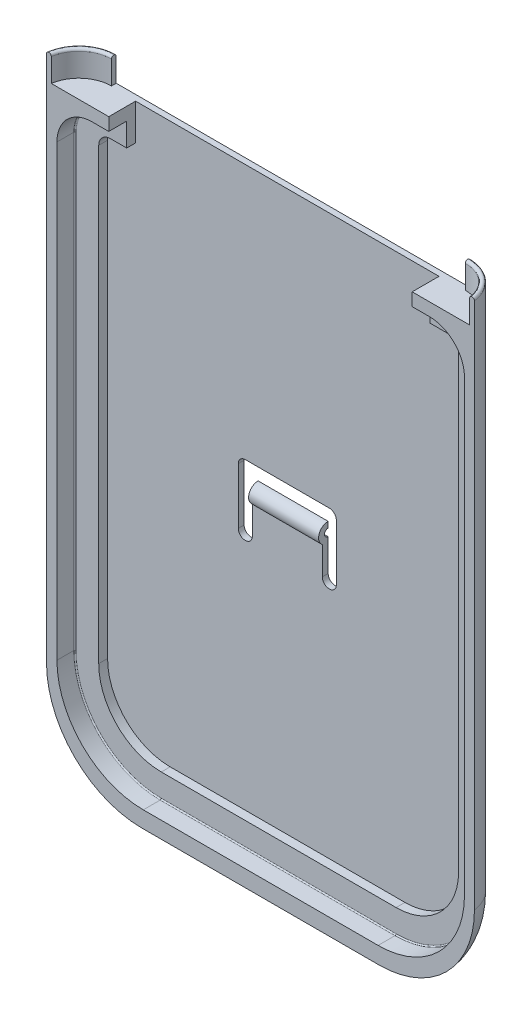
SolidWorks part; units mm, degrees
ref_plane "Front" through (0, 0, 0) normal (0, 0, 1) x (1, 0, 0)
ref_plane "Top" through (0, 0, 0) normal (0, 1, 0) x (1, 0, 0)
ref_plane "Right" through (0, 0, 0) normal (1, 0, 0) x (0, 0, -1)
ref_plane "Plane4" through (0, 0, -6.7818) normal (0, 0, 1) x (1, 0, 0)
sketch "Sketch14" plane through (0, 0, -6.7818) normal (0, 0, 1) x (1, 0, 0)
  line L3 (23.2853, 10.3821) -> (23.2853, 68.0401)
  line L4 (-12.9032, 0) -> (12.9032, 0)
  line L5 (-23.2853, 68.0401) -> (-23.2853, 10.3821)
  line L6 (23.2853, 68.0401) -> (-23.2853, 68.0401)
  arc A2 (12.9032, 0) -> (23.2853, 10.3821) centre (12.9032, 10.3821) ccw
  arc A3 (-23.2853, 10.3821) -> (-12.9032, 0) centre (-12.9032, 10.3821) ccw
  dimension "D3" = 10.3821
  dimension "D4" = 10.3821
  dimension "D1" = 46.5706
  dimension "D2" = 68.0401
extrude "Boss-Extrude11" add sketch "Sketch14" along normal blind 3.556 separate body
fillet "Fillet37" radius 4.064 5 edges at (-23.2853, 39.2111, -6.7818) (-20.2445, 3.0409, -6.7818) (0, 0, -6.7818) (20.2445, 3.0409, -6.7818) (23.2853, 39.2111, -6.7818)
sketch "Sketch15" plane through (0, 0, -3.2258) normal (0, 0, 1) x (1, 0, 0)
  line L0 (0, -50) -> (0, 50) construction
  line L3 (-22.1488, 63.8491) -> (22.1995, 63.8491)
  line L4 (22.1995, 63.8491) -> (22.1995, 11.1949)
  line L5 (12.8015, 1.7969) -> (-12.7508, 1.7969)
  line L6 (23.2853, 68.0401) -> (-23.2853, 68.0401) construction
  line L8 (-12.9032, 0) -> (12.9032, 0) construction
  line L11 (-22.1488, 63.8491) -> (-22.1488, 11.1949)
  arc A1 (12.8015, 1.7969) -> (22.1995, 11.1949) centre (12.8015, 11.1949) ccw
  arc A2 (-12.7508, 1.7969) -> (-22.1488, 11.1949) centre (-12.7508, 11.1949) cw
  point P19 (0, 63.8491)
  dimension "D3" = 9.398
  dimension "D1" = 4.191
  dimension "D2" = 22.1995
  dimension "D4" = 1.7969
  dimension "D5" = 22.1488
extrude "Cut-Extrude2" cut sketch "Sketch15" against normal blind 1.9558
sketch "Sketch16" plane through (0, 0, -5.1816) normal (0, 0, 1) x (1, 0, 0)
  line L4 (19.6088, 61.3091) -> (19.6088, 11.1949)
  line L5 (12.8016, 4.3877) -> (-12.7508, 4.3877)
  line L6 (-19.558, 11.1949) -> (-19.558, 61.3091)
  line L7 (-19.558, 61.3091) -> (19.6088, 61.3091)
  line L10 (22.1995, 63.8491) -> (-22.1488, 63.8491) construction
  line L11 (-12.7508, 1.7969) -> (12.8015, 1.7969) construction
  arc A0 (12.8016, 4.3877) -> (19.6088, 11.1949) centre (12.8016, 11.1949) ccw
  arc A1 (-12.7508, 4.3877) -> (-19.558, 11.1949) centre (-12.7508, 11.1949) cw
  dimension "D2" = 6.8072
  dimension "D1" = 19.6088
  dimension "D3" = 2.54
  dimension "D4" = 2.5908
  dimension "D5" = 19.558
extrude "Cut-Extrude3" cut sketch "Sketch16" against normal blind 0.9652
ref_plane "Plane1" through (13.8684, 0, 0) normal (1, 0, 0) x (0, 0, -1)
ref_plane "Plane6" through (0, 0, -1.8288) normal (0, 0, -1) x (-1, 0, 0)
sketch "Sketch18" plane through (0, 0, -1.8288) normal (0, 0, 1) x (1, 0, 0)
  line L4 (-19.558, 21.5886) -> (19.6088, 21.5886)
  line L5 (19.6088, 21.9696) -> (-19.558, 21.9696)
  line L6 (17.5599, 3.1939) -> (-19.1347, 3.1939)
  line L7 (-20.3708, 7.1055) -> (-20.3708, 61.7257)
  line L8 (-20.3708, 61.7257) -> (20.4216, 61.7257)
  line L9 (-19.558, 39.1705) -> (19.6088, 39.1705)
  line L10 (19.6088, 39.5515) -> (-19.558, 39.5515)
  line L11 (20.4216, 8.7411) -> (20.4216, 61.7257)
  line L12 (19.6088, 39.5515) -> (19.6088, 61.3091)
  line L13 (19.6088, 21.9696) -> (19.6088, 39.1705)
  line L14 (-19.558, 21.5886) -> (-19.558, 11.1949)
  line L15 (-19.558, 39.1705) -> (-19.558, 21.9696)
  line L16 (-12.7508, 4.3877) -> (12.8016, 4.3877)
  line L17 (19.6088, 11.1949) -> (19.6088, 61.3091)
  line L18 (19.6088, 61.3091) -> (-19.558, 61.3091)
  line L19 (-19.558, 61.3091) -> (-19.558, 11.1949)
  line L20 (-12.7508, 4.3877) -> (12.8016, 4.3877)
  line L21 (19.6088, 11.1949) -> (19.6088, 21.5886)
  line L22 (19.6088, 61.3091) -> (-19.558, 61.3091)
  line L23 (-19.558, 61.3091) -> (-19.558, 39.5515)
  arc A2 (-20.3708, 7.1055) -> (-19.1347, 3.1939) centre (-13.5636, 7.1055) ccw
  arc A3 (17.5599, 3.1939) -> (20.4216, 8.7411) centre (13.6144, 8.7411) ccw
  arc A4 (-19.558, 11.1949) -> (-12.7508, 4.3877) centre (-12.7508, 11.1949) ccw
  arc A5 (-19.558, 11.1949) -> (-12.7508, 4.3877) centre (-12.7508, 11.1949) ccw
  arc A6 (12.8016, 4.3877) -> (19.6088, 11.1949) centre (12.8016, 11.1949) ccw
  arc A7 (12.8016, 4.3877) -> (19.6088, 11.1949) centre (12.8016, 11.1949) ccw
  dimension "D4" = 6.8072
  dimension "D6" = 6.8072
  dimension "D2" = 0.4166
  dimension "D3" = 0.8128
  dimension "D5" = 1.1938
  dimension "D7" = 0.8128
  dimension "D8" = 36.6946
  dimension "D9" = 0.4233
  dimension "D10" = 17.2009
  dimension "D11" = 0.381
  dimension "D12" = 0.381
  dimension "D13" = 17.5819
  dimension "D1" = 0
extrude "Boss-Extrude12" [suppressed] add sketch "Sketch18" against normal up to surface (4.445 mm away) up to face at (0.0254, 25.1607, -6.1468)
ref_plane "Plane5" [suppressed] through (-0.0255, 0, 0) normal (-1, 0, 0) x (0, 0, 1)
sketch "Sketch19" [suppressed] plane through (0, 0, 0) normal (1, 0, 0) x (0, 0, -1)
  line L2 (4.2171, 0.7825) -> (1.8288, 0.7825)
  line L3 (6.1468, 2.7685) -> (6.1468, 7.2833)
  line L5 (1.8288, 7.2833) -> (5.1816, 7.2833) construction
  line L6 (1.8288, 7.2833) -> (6.1468, 7.2833)
  line L7 (1.8288, 7.2833) -> (1.8288, 0.7825)
  arc A0 (4.2171, 0.7825) -> (5.2167, 1.1561) centre (4.2171, 2.3065) ccw construction
  arc A1 (5.2167, 1.1561) -> (5.8928, 1.9261) centre (2.7178, 4.0321) ccw construction
  arc A2 (5.8928, 1.9261) -> (6.1468, 2.7685) centre (4.6228, 2.7685) ccw construction
  arc A3 (4.2171, 0.7825) -> (5.2167, 1.1561) centre (4.2171, 2.3065) ccw
  arc A4 (5.2167, 1.1561) -> (5.8928, 1.9261) centre (2.7178, 4.0321) ccw
  arc A5 (5.8928, 1.9261) -> (6.1468, 2.7685) centre (4.6228, 2.7685) ccw
extrude "Cut-Extrude9" [suppressed] cut sketch "Sketch19" against normal blind 12.8016 and the other way blind 6.35
sketch "Sketch1" [suppressed] plane through (13.8684, 0, 0) normal (1, 0, 0) x (0, 0, -1)
  line L0 (3.3744, 8.4771) -> (6.2738, 8.4771)
  line L1 (6.2738, 8.4771) -> (6.2738, 11.292)
  line L2 (6.2738, 8.4771) -> (1.8288, 8.4771) construction
  line L3 (6.2738, 25.678) -> (6.2738, 9.2391) construction
  line L4 (6.2738, 25.678) -> (1.8288, 25.678) construction
  line L5 (3.3731, 25.678) -> (6.2738, 25.678)
  line L6 (6.2738, 25.678) -> (6.2738, 22.7773)
  line L7 (6.2738, 26.059) -> (1.8288, 26.059) construction
  line L8 (6.2738, 43.2599) -> (6.2738, 26.059) construction
  line L9 (3.3731, 26.059) -> (6.2738, 26.059)
  line L10 (6.2738, 26.059) -> (6.2738, 28.9597)
  line L11 (6.2738, 43.2599) -> (1.8288, 43.2599) construction
  line L12 (3.3731, 43.2599) -> (6.2738, 43.2599)
  line L13 (6.2738, 43.2599) -> (6.2738, 40.3592)
  line L15 (6.2738, 43.6409) -> (1.8288, 43.6409) construction
  line L16 (6.2738, 43.6409) -> (6.2738, 60.8418) construction
  line L17 (3.3731, 43.6409) -> (6.2738, 43.6409)
  line L18 (6.2738, 43.6409) -> (6.2738, 46.5416)
  line L19 (6.2738, 60.8418) -> (3.3731, 60.8418)
  line L20 (6.2738, 60.8418) -> (1.8288, 60.8418) construction
  line L21 (6.2738, 60.8418) -> (6.2738, 57.9411)
  arc A0 (6.2738, 11.292) -> (3.3744, 8.4771) centre (3.3744, 11.3778) cw
  arc A1 (3.3731, 25.678) -> (6.2738, 22.7773) centre (3.3731, 22.7773) cw
  arc A2 (3.3731, 26.059) -> (6.2738, 28.9597) centre (3.3731, 28.9597) ccw
  arc A3 (3.3731, 43.2599) -> (6.2738, 40.3592) centre (3.3731, 40.3592) cw
  arc A4 (3.3731, 43.6409) -> (6.2738, 46.5416) centre (3.3731, 46.5416) ccw
  arc A5 (3.3731, 60.8418) -> (6.2738, 57.9411) centre (3.3731, 57.9411) cw
  dimension "D1" = 2.9007
  dimension "D2" = 2.8994
extrude "Boss-Extrude1" [suppressed] add sketch "Sketch1" against normal blind 0.762
sketch "Sketch22" plane through (0, 68.0401, 0) normal (0, 1, 0) x (1, 0, 0)
  line L3 (-19.2532, 6.7818) -> (-19.2532, 6.2611)
  line L4 (19.2532, 6.2611) -> (19.2532, 6.7818)
  line L5 (22.1995, 3.2258) -> (-22.1488, 3.2258) construction
  line L7 (22.7599, 3.2258) -> (-22.7599, 3.2258)
  line L8 (19.2532, 6.7818) -> (-19.2532, 6.7818)
  line L10 (19.2532, 6.7818) -> (-19.2532, 6.7818) construction
  line L11 (0, 0) -> (0, 6.7818) construction
  arc A7 (22.7687, 3.1607) -> (19.2532, 6.2611) centre (19.2532, 2.7178) ccw
  arc A8 (22.7599, 3.2258) -> (19.2532, 6.2611) centre (19.2532, 2.7178) ccw
  arc A9 (-19.2532, 6.2611) -> (-22.7687, 3.1607) centre (-19.2532, 2.7178) ccw
  arc A10 (-19.2532, 6.2611) -> (-22.7599, 3.2258) centre (-19.2532, 2.7178) ccw
  dimension "D2" = 0.5207
  dimension "D5" = 0.5207
  dimension "D1" = 38.5064
extrude "Cut-Extrude7" cut sketch "Sketch22" against normal blind 2.794
fillet "Fillet38" [suppressed] type full round
fillet "Fillet39" [suppressed] type full round
ref_plane "Plane2" [suppressed] through (29.6672, 0, 0) normal (-1, 0, 0) x (0, -1, 0)
ref_plane "Plane10" [suppressed] through (6.35, 0, 0) normal (1, 0, 0) x (0, 0, -1)
sketch "Sketch2" [suppressed] plane through (6.35, 0, 0) normal (-1, 0, 0) x (0, -1, 0)
  line L0 (-11.292, -6.2738) -> (-8.4771, -6.2738) construction
  line L1 (-8.4771, -6.2738) -> (-8.4771, -3.3744) construction
  line L5 (-25.678, -3.3731) -> (-25.678, -6.2738) construction
  line L6 (-25.678, -6.2738) -> (-22.7773, -6.2738) construction
  line L9 (-28.9597, -6.2738) -> (-26.059, -6.2738) construction
  line L10 (-26.059, -6.2738) -> (-26.059, -3.3731) construction
  line L12 (-43.2599, -3.3731) -> (-43.2599, -6.2738) construction
  line L13 (-43.2599, -6.2738) -> (-40.3592, -6.2738) construction
  line L18 (-46.5416, -6.2738) -> (-43.6409, -6.2738) construction
  line L19 (-43.6409, -6.2738) -> (-43.6409, -3.3731) construction
  line L20 (-60.8418, -6.2738) -> (-57.9411, -6.2738) construction
  line L21 (-60.8418, -3.3731) -> (-60.8418, -6.2738) construction
  line L22 (-11.292, -6.2738) -> (-8.4771, -6.2738)
  line L23 (-8.4771, -6.2738) -> (-8.4771, -3.3744)
  line L24 (-25.678, -3.3731) -> (-25.678, -6.2738)
  line L25 (-25.678, -6.2738) -> (-22.7773, -6.2738)
  line L26 (-28.9597, -6.2738) -> (-26.059, -6.2738)
  line L27 (-26.059, -6.2738) -> (-26.059, -3.3731)
  line L28 (-43.2599, -3.3731) -> (-43.2599, -6.2738)
  line L29 (-43.2599, -6.2738) -> (-40.3592, -6.2738)
  line L30 (-46.5416, -6.2738) -> (-43.6409, -6.2738)
  line L31 (-43.6409, -6.2738) -> (-43.6409, -3.3731)
  line L32 (-60.8418, -6.2738) -> (-57.9411, -6.2738)
  line L33 (-60.8418, -3.3731) -> (-60.8418, -6.2738)
  arc A0 (-11.292, -6.2738) -> (-8.4771, -3.3744) centre (-11.3778, -3.3744) ccw construction
  arc A1 (-25.678, -3.3731) -> (-22.7773, -6.2738) centre (-22.7773, -3.3731) ccw construction
  arc A2 (-28.9597, -6.2738) -> (-26.059, -3.3731) centre (-28.9597, -3.3731) ccw construction
  arc A3 (-43.2599, -3.3731) -> (-40.3592, -6.2738) centre (-40.3592, -3.3731) ccw construction
  arc A6 (-46.5416, -6.2738) -> (-43.6409, -3.3731) centre (-46.5416, -3.3731) ccw construction
  arc A7 (-60.8418, -3.3731) -> (-57.9411, -6.2738) centre (-57.9411, -3.3731) ccw construction
  arc A8 (-11.292, -6.2738) -> (-8.4771, -3.3744) centre (-11.3778, -3.3744) ccw
  arc A9 (-25.678, -3.3731) -> (-22.7773, -6.2738) centre (-22.7773, -3.3731) ccw
  arc A10 (-28.9597, -6.2738) -> (-26.059, -3.3731) centre (-28.9597, -3.3731) ccw
  arc A11 (-43.2599, -3.3731) -> (-40.3592, -6.2738) centre (-40.3592, -3.3731) ccw
  arc A12 (-46.5416, -6.2738) -> (-43.6409, -3.3731) centre (-46.5416, -3.3731) ccw
  arc A13 (-60.8418, -3.3731) -> (-57.9411, -6.2738) centre (-57.9411, -3.3731) ccw
extrude "Boss-Extrude2" [suppressed] add sketch "Sketch2" against normal blind 0.762
sketch "Sketch3" [suppressed] plane through (6.35, 0, 0) normal (-1, 0, 0) x (0, -1, 0)
  line L0 (-60.8418, -3.3744) -> (-60.8418, -6.2738)
  line L1 (-60.8418, -6.2738) -> (-58.0269, -6.2738)
  line L2 (-60.8418, -6.2738) -> (-60.8418, -1.8288) construction
  line L3 (-60.8418, -6.2738) -> (-43.6409, -6.2738) construction
  line L4 (-43.6409, -6.2738) -> (-43.6409, -1.8288) construction
  line L5 (-43.6409, -3.3731) -> (-43.6409, -6.2738)
  line L6 (-43.6409, -6.2738) -> (-46.5416, -6.2738)
  arc A0 (-58.0269, -6.2738) -> (-60.8418, -3.3744) centre (-57.9411, -3.3744) cw
  arc A1 (-43.6409, -3.3731) -> (-46.5416, -6.2738) centre (-46.5416, -3.3731) cw
  dimension "D1" = 2.9007
  dimension "D2" = 2.8149
sketch "Sketch9" [suppressed] plane through (0, 0, -6.2738) normal (0, 0, 1) x (1, 0, 0)
  line L0 (16.4084, 37.1994) -> (17.0434, 37.1994)
  line L1 (17.0434, 37.1994) -> (17.0434, 32.1194)
  line L2 (17.0434, 32.1194) -> (16.4084, 32.1194)
  line L3 (16.4084, 32.1194) -> (16.4084, 37.1994)
  line L4 (-18.796, 34.6594) -> (16.4084, 34.6594) construction
  line L5 (50, 0) -> (-50, 0) construction
  line L7 (18.7452, 26.059) -> (18.7452, 43.2599) construction
  line L9 (16.4084, 19.6176) -> (17.0434, 19.6176)
  line L10 (16.4084, 19.6176) -> (16.4084, 14.5376)
  line L11 (16.4084, 14.5376) -> (17.0434, 14.5376)
  line L12 (17.0434, 19.6176) -> (17.0434, 14.5376)
  line L13 (16.4084, 54.7813) -> (17.0434, 54.7813)
  line L14 (16.4084, 54.7813) -> (16.4084, 49.7013)
  line L15 (16.4084, 49.7013) -> (17.0434, 49.7013)
  line L16 (17.0434, 54.7813) -> (17.0434, 49.7013)
  line L18 (-18.796, 43.2599) -> (-18.796, 26.059) construction
  line L20 (-18.796, 52.2413) -> (16.4084, 52.2413) construction
  line L22 (-18.796, 17.0776) -> (16.4084, 17.0776) construction
  dimension "D1" = 1.7018
  dimension "D2" = 0.635
  dimension "D3" = 52.2413
  dimension "D4" = 5.08
  dimension "D5" = 17.0776
  dimension "D6" = 5.08
  dimension "D8" = 5.08
extrude "Boss-Extrude8" [suppressed] add sketch "Sketch9" along normal blind 3.175
sketch "Sketch8" plane through (0, 0, -3.2258) normal (0, 0, 1) x (1, 0, 0)
  line L0 (-16.51, 65.2461) -> (-16.51, 64.6111)
  line L1 (-16.51, 64.6111) -> (16.51, 64.6111)
  line L2 (16.51, 64.6111) -> (16.51, 65.2461)
  line L3 (16.51, 65.2461) -> (-16.51, 65.2461)
  line L4 (0, -50) -> (0, 50) construction
  line L6 (-22.7599, 65.2461) -> (22.7599, 65.2461) construction
  point P8 (0, 64.6111)
  dimension "D1" = 0.635
  dimension "D3" = 33.02
extrude "Cut-Extrude1" [suppressed] cut sketch "Sketch8" against normal blind 1.9558
mirror "Mirror1" [suppressed] about plane through (0, 0, 0) normal (1, 0, 0)
sketch "Sketch25" [suppressed] plane through (0, 0, 0) normal (1, 0, 0) x (0, 0, -1)
  line L0 (3.3731, 25.678) -> (3.3731, 26.059)
  line L1 (-0.2883, 28.0707) -> (0.612, 28.0707)
  line L2 (0.612, 23.6663) -> (-0.2883, 23.6663)
  line L3 (6.2738, 26.059) -> (1.8288, 26.059) construction
  line L6 (-0.2883, 41.2482) -> (-0.2883, 45.6526)
  line L7 (0.612, 45.6526) -> (-0.2883, 45.6526)
  line L8 (-0.2883, 41.2482) -> (0.612, 41.2482)
  line L9 (3.3692, 43.6409) -> (3.3692, 43.2599)
  line L10 (3.3692, 43.4504) -> (-0.2883, 43.4504) construction
  line L11 (-0.2883, 28.0707) -> (-0.2883, 23.6663)
  line L12 (3.3731, 25.8685) -> (-0.2883, 25.8685) construction
  line L13 (0, 50) -> (0, -50) construction
  arc A0 (6.2738, 22.7773) -> (3.3731, 25.678) centre (3.3731, 22.7773) ccw construction
  arc A1 (3.3731, 26.059) -> (6.2738, 28.9597) centre (3.3731, 28.9597) ccw construction
  arc A2 (3.3731, 43.6409) -> (6.2738, 46.5416) centre (3.3731, 46.5416) ccw construction
  arc A4 (3.3692, 43.6409) -> (0.612, 45.6526) centre (3.3731, 46.5416) cw
  arc A5 (0.612, 41.2482) -> (3.3692, 43.2599) centre (3.3731, 40.3592) cw
  arc A7 (6.2738, 40.3592) -> (3.3731, 43.2599) centre (3.3731, 40.3592) ccw construction
  arc A9 (0.612, 28.0707) -> (3.3731, 26.059) centre (3.3731, 28.9597) ccw
  arc A10 (3.3731, 25.678) -> (0.612, 23.6663) centre (3.3731, 22.7773) ccw
  dimension "D1" = 0.2883
  dimension "D2" = 4.4044
  dimension "D3" = 4.4044
extrude "Boss-Extrude13" [suppressed] add sketch "Sketch25" along normal up to surface and the other way up to surface up to face at (22.1995, 37.522, -4.2037)
fillet "Fillet40" [suppressed] type full round
fillet "Fillet41" [suppressed] type full round
fillet "Fillet42" [suppressed] type full round
fillet "Fillet43" [suppressed] type full round
ref_plane "Plane3" [suppressed] through (23.3172, 0, 0) normal (-1, 0, 0) x (0, 0, 1)
sketch "Sketch12" [suppressed] plane through (0, 0, 0) normal (-1, 0, 0) x (0, 0, 1)
  line L0 (-6.2738, 8.4771) -> (-1.8288, 8.4771) construction
  line L1 (-1.8288, 8.0961) -> (-3.3744, 8.0961)
  line L2 (-3.3744, 8.0961) -> (-3.3744, 8.4771)
  arc A0 (-1.8288, 8.0961) -> (0.0047, 9.9565) centre (-3.2677, 11.348) ccw
  arc A1 (0.0047, 9.9565) -> (-0.7001, 10.2544) centre (-0.3474, 10.1062) ccw
  arc A2 (-0.7001, 10.2544) -> (-3.3744, 8.4771) centre (-3.3744, 11.3778) cw
  dimension "D1" = 10.1062
  dimension "D2" = 0.3826
  dimension "D3" = 0.3474
  dimension "D4" = 2.9007
  dimension "D6" = 3.556
  dimension "D7" = 3.2677
  dimension "D5" = 1.5456
sketch "Sketch13" [suppressed] plane through (0, 0, 0) normal (-1, 0, 0) x (0, 0, 1)
  line L0 (-1.8288, 61.2583) -> (-3.3744, 61.2583)
  line L1 (-5.1816, 61.2583) -> (-1.8288, 61.2583) construction
  line L2 (-3.3744, 61.2583) -> (-3.3744, 60.8418)
  line L3 (-1.8288, 61.2583) -> (-1.8288, 61.2228)
  line L4 (-1.8288, 61.2583) -> (-1.8288, 11.1949) construction
  line L5 (50, 0) -> (-50, 0) construction
  line L6 (0, -50) -> (0, 50) construction
  arc A0 (-3.3744, 60.8418) -> (-0.7001, 59.0645) centre (-3.3744, 57.9411) cw
  arc A1 (-0.7001, 59.0645) -> (0.0047, 59.3624) centre (-0.3474, 59.2127) ccw
  arc A4 (0.0047, 59.3624) -> (-1.8288, 61.2228) centre (-3.2677, 57.9709) ccw
  dimension "D1" = 2.9007
  dimension "D2" = 3.556
  dimension "D3" = 59.2127
  dimension "D6" = 57.9411
  dimension "D7" = 57.9709
  dimension "D4" = 0.3474
  dimension "D5" = 1.5456
sketch "Sketch20" [suppressed] plane through (0, 0, -6.2738) normal (0, 0, 1) x (1, 0, 0)
  line L0 (19.558, 61.2583) -> (-19.6088, 61.2583) construction
  line L1 (-6.3754, 29.869) -> (6.3246, 29.869)
  line L2 (-6.3754, 29.869) -> (-6.3754, 21.868)
  line L3 (-6.3754, 21.868) -> (6.3246, 21.868)
  line L4 (6.3246, 29.869) -> (6.3246, 21.868)
  line L5 (-6.3754, 47.4509) -> (6.3246, 47.4509)
  line L6 (-6.3754, 47.4509) -> (-6.3754, 39.4499)
  line L7 (-6.3754, 39.4499) -> (6.3246, 39.4499)
  line L8 (6.3246, 47.4509) -> (6.3246, 39.4499)
  line L9 (6.3246, 60.8418) -> (-6.3754, 60.8418)
  line L10 (6.3246, 60.8418) -> (6.3246, 57.0318)
  line L11 (6.3246, 57.0318) -> (-6.3754, 57.0318)
  line L12 (-6.3754, 60.8418) -> (-6.3754, 57.0318)
  line L13 (-6.3754, 8.4771) -> (6.3246, 8.4771)
  line L14 (-6.3754, 8.4771) -> (-6.3754, 12.2871)
  line L15 (-6.3754, 12.2871) -> (6.3246, 12.2871)
  line L16 (6.3246, 8.4771) -> (6.3246, 12.2871)
  line L18 (18.7452, 60.8418) -> (-18.796, 60.8418) construction
  line L21 (-0.0254, 61.2583) -> (-0.0254, 60.8418) construction
  line L23 (-18.034, 8.4771) -> (17.9832, 8.4771) construction
  line L24 (-18.796, 26.059) -> (-18.796, 25.678) construction
  line L25 (-18.796, 25.8685) -> (-6.3754, 25.8685) construction
  line L26 (-18.796, 43.6409) -> (-18.796, 43.2599) construction
  line L27 (-18.796, 43.4504) -> (-6.3754, 43.4504) construction
  dimension "D1" = 12.7
  dimension "D2" = 3.81
  dimension "D3" = 8.001
  dimension "D4" = 3.81
extrude "Cut-Extrude5" [suppressed] cut sketch "Sketch20" against normal through all
sketch "Sketch21" [suppressed] plane through (0, 0, -1.8288) normal (0, 0, 1) x (1, 0, 0)
  line L1 (19.558, 58.6091) -> (18.7452, 58.6091)
  line L2 (19.558, 58.6091) -> (19.558, 47.329)
  line L3 (19.558, 47.329) -> (18.7452, 47.329)
  line L4 (18.7452, 58.6091) -> (18.7452, 47.329)
  line L7 (19.558, 41.0183) -> (18.7452, 41.0183)
  line L8 (19.558, 41.0183) -> (19.558, 29.7382)
  line L9 (19.558, 29.7382) -> (18.7452, 29.7382)
  line L10 (18.7452, 41.0183) -> (18.7452, 29.7382)
  line L12 (19.558, 23.439) -> (18.7452, 23.439)
  line L13 (19.558, 23.439) -> (19.558, 12.1589)
  line L14 (19.558, 12.1589) -> (18.7452, 12.1589)
  line L15 (18.7452, 23.439) -> (18.7452, 12.1589)
  line L22 (18.7452, 43.6409) -> (18.7452, 60.8418) construction
  line L23 (19.558, 11.1949) -> (19.558, 61.2583) construction
  line L24 (18.7452, 60.8418) -> (-18.796, 60.8418) construction
  line L25 (18.7452, 43.2599) -> (6.35, 43.2599) construction
  line L26 (18.7452, 26.059) -> (18.7452, 43.2599) construction
  line L27 (18.7452, 9.2391) -> (18.7452, 25.678) construction
  line L28 (18.7452, 25.678) -> (6.35, 25.678) construction
  dimension "D1" = 11.2801
  dimension "D2" = 2.2327
  dimension "D3" = 11.2801
  dimension "D4" = 2.2416
  dimension "D5" = 11.2801
  dimension "D6" = 2.239
extrude "Cut-Extrude6" [suppressed] cut sketch "Sketch21" against normal up to surface (3.3528 mm away) up to face at (0.0254, 25.1607, -5.1816)
ref_plane "Plane7" [suppressed] through (-5.842, 0, 0) normal (-1, 0, 0) x (0, 0, 1)
sketch "Sketch26" [suppressed] plane through (-5.842, 0, 0) normal (-1, 0, 0) x (0, 0, 1)
  line L0 (0.2883, 24.2012) -> (0.2883, 27.5358) construction
  line L1 (0.2883, 41.783) -> (0.2883, 45.1177) construction
  line L2 (0.2883, 41.7562) -> (-0.2651, 41.7562)
  line L3 (-0.2651, 45.1446) -> (0.2883, 45.1446)
  line L4 (0.2883, 45.1446) -> (0.2883, 41.7562)
  line L7 (0.2883, 27.5627) -> (-0.2651, 27.5627)
  line L8 (-0.2651, 24.1743) -> (0.2883, 24.1743)
  line L9 (0.2883, 27.5627) -> (0.2883, 24.1743)
  arc A0 (-0.2651, 41.7562) -> (-1.546, 43.236) centre (-3.3744, 40.3592) ccw construction
  arc A1 (-0.2651, 24.1743) -> (-1.546, 25.6541) centre (-3.3744, 22.7773) ccw construction
  arc A2 (-1.546, 26.0829) -> (-0.2651, 27.5627) centre (-3.3744, 28.9597) ccw construction
  arc A3 (-1.546, 43.6648) -> (-0.2651, 45.1446) centre (-3.3744, 46.5416) ccw construction
  arc A7 (-1.9378, 43.4504) -> (-0.2651, 45.1446) centre (-3.3744, 46.5416) ccw
  arc A13 (-1.9378, 25.8685) -> (-0.2651, 27.5627) centre (-3.3744, 28.9597) ccw
  arc A16 (-0.2651, 24.1743) -> (-1.9378, 25.8685) centre (-3.3744, 22.7773) ccw
  arc A18 (-0.2651, 41.7562) -> (-1.9378, 43.4504) centre (-3.3744, 40.3592) ccw
  dimension "D5" = 3.3884
  dimension "D6" = 3.3884
extrude "Cut-Extrude8" [suppressed] cut sketch "Sketch26" against normal blind 11.684
fillet "Fillet27" [suppressed] radius 1.524 tangent propagation no
fillet "Fillet44" [suppressed] radius 0.381
fillet "Fillet45" [suppressed] radius 0.762
fillet "Fillet47" [suppressed] radius 1.524
fillet "Fillet48" [suppressed] radius 1.524
fillet "Fillet49" [suppressed] radius 3.81
sketch "Sketch27" [suppressed] plane through (0, 0, -5.1816) normal (0, 0, 1) x (1, 0, 0)
  line L0 (18.7452, 44.4029) -> (18.7452, 60.0798) construction
  line L1 (18.7452, 56.5771) -> (19.558, 56.5771)
  line L2 (18.7452, 56.5771) -> (18.7452, 49.361)
  line L3 (18.7452, 49.361) -> (19.558, 49.361)
  line L4 (19.558, 56.5771) -> (19.558, 49.361)
  line L5 (18.7452, 26.821) -> (18.7452, 42.4979) construction
  line L6 (18.7452, 38.9863) -> (19.558, 38.9863)
  line L7 (18.7452, 38.9863) -> (18.7452, 31.7702)
  line L8 (18.7452, 31.7702) -> (19.558, 31.7702)
  line L9 (19.558, 38.9863) -> (19.558, 31.7702)
  line L10 (18.7452, 9.2391) -> (18.7452, 24.916) construction
  line L11 (18.7452, 21.407) -> (19.558, 21.407)
  line L12 (18.7452, 21.407) -> (18.7452, 14.1909)
  line L13 (18.7452, 14.1909) -> (19.558, 14.1909)
  line L14 (19.558, 21.407) -> (19.558, 14.1909)
  line L16 (18.7452, 41.0183) -> (19.558, 41.0183) construction
  line L17 (19.558, 58.6091) -> (18.7452, 58.6091) construction
  line L18 (19.558, 41.0183) -> (18.7452, 41.0183) construction
  line L19 (18.7452, 23.439) -> (19.558, 23.439) construction
  dimension "D1" = 7.2161
  dimension "D2" = 2.032
  dimension "D3" = 2.032
  dimension "D4" = 2.032
extrude "Boss-Extrude14" [suppressed] add sketch "Sketch27" along normal up to surface (3.3528 mm away) up to face at (0.0254, 25.1607, -5.1816)
sketch "Sketch30" [suppressed] plane through (0, 0, -6.2738) normal (0, 0, -1) x (-1, 0, 0)
  line L4 (-6.3246, 43.6409) -> (-6.3246, 43.2599)
  line L5 (-6.3246, 43.2599) -> (6.35, 43.2599)
  line L6 (6.3754, 40.9739) -> (6.3754, 45.9269)
  line L7 (6.35, 43.6409) -> (-6.3246, 43.6409)
  line L8 (-6.3246, 43.6409) -> (-6.3246, 43.2599)
  line L9 (-6.3246, 43.2599) -> (6.35, 43.2599)
  line L10 (6.3754, 40.9739) -> (6.3754, 45.9269)
  line L11 (6.35, 43.6409) -> (-6.3246, 43.6409)
  line L12 (-6.3246, 26.059) -> (-6.3246, 25.678)
  line L13 (-6.3246, 25.678) -> (6.35, 25.678)
  line L14 (6.3754, 23.392) -> (6.3754, 28.345)
  line L15 (6.35, 26.059) -> (-6.3246, 26.059)
  line L16 (-6.3246, 26.059) -> (-6.3246, 25.678)
  line L17 (-6.3246, 25.678) -> (6.35, 25.678)
  line L18 (6.3754, 23.392) -> (6.3754, 28.345)
  line L19 (6.35, 26.059) -> (-6.3246, 26.059)
  line L22 (6.35, 46.204) -> (6.35, 43.6409)
  line L23 (6.35, 46.204) -> (6.35, 43.6409)
  line L24 (6.35, 43.2599) -> (6.35, 40.6968)
  line L25 (6.35, 43.2599) -> (6.35, 40.6968)
  line L26 (6.35, 28.6221) -> (6.35, 26.059)
  line L27 (6.35, 28.6221) -> (6.35, 26.059)
  line L28 (6.35, 25.678) -> (6.35, 23.1149)
  line L29 (6.35, 25.678) -> (6.35, 23.1149)
  arc A2 (6.3754, 45.9269) -> (6.35, 46.204) centre (4.8514, 45.9269) ccw
  arc A3 (6.3754, 45.9269) -> (6.35, 46.204) centre (4.8514, 45.9269) ccw
  arc A4 (6.35, 40.6968) -> (6.3754, 40.9739) centre (4.8514, 40.9739) ccw
  arc A5 (6.35, 40.6968) -> (6.3754, 40.9739) centre (4.8514, 40.9739) ccw
  arc A6 (6.3754, 28.345) -> (6.35, 28.6221) centre (4.8514, 28.345) ccw
  arc A7 (6.3754, 28.345) -> (6.35, 28.6221) centre (4.8514, 28.345) ccw
  arc A8 (6.35, 23.1149) -> (6.3754, 23.392) centre (4.8514, 23.392) ccw
  arc A9 (6.35, 23.1149) -> (6.3754, 23.392) centre (4.8514, 23.392) ccw
  dimension "D1" = 0
  dimension "D2" = 0
extrude "Boss-Extrude17" [suppressed] add sketch "Sketch30" along normal up to surface (0.508 mm away) up to face at (0, 26.1151, -6.7818)
fillet "Fillet51" [suppressed] radius 0.254
fillet "Fillet52" radius 3.81 2 edges at (-22.1488, 63.8491, -4.2037) (22.1995, 63.8491, -4.2037)
fillet "Fillet53" radius 1.27 2 edges at (19.6088, 61.3091, -5.6642) (-19.558, 61.3091, -5.6642)
sketch "Sketch31" plane through (0, 0, -3.2258) normal (0, 0, 1) x (1, 0, 0)
  line L0 (-22.7599, 65.2461) -> (22.7599, 65.2461) construction
  line L1 (-16.51, 65.2461) -> (16.51, 65.2461)
  line L2 (-16.51, 65.2461) -> (-16.51, 55.3049)
  line L3 (-16.51, 55.3049) -> (16.51, 55.3049)
  line L4 (16.51, 65.2461) -> (16.51, 55.3049)
  point P6 (0, 65.2461)
  dimension "D1" = 33.02
extrude "Cut-Extrude10" cut sketch "Sketch31" against normal up to surface (2.921 mm away) up to face at (0.0254, 33.946, -6.1468)
sketch "Sketch32" plane through (0, 0, -6.1468) normal (0, 0, 1) x (1, 0, 0)
  line L0 (0, 29.8129) -> (0, 0) construction
  line L1 (-5.334, 37.4329) -> (5.334, 37.4329)
  line L2 (-5.334, 37.4329) -> (-5.334, 29.8129)
  line L3 (-5.334, 29.8129) -> (5.334, 29.8129)
  line L4 (5.334, 37.4329) -> (5.334, 29.8129)
  line L5 (16.51, 65.2461) -> (-16.51, 65.2461) construction
  dimension "D1" = 10.668
  dimension "D2" = 7.62
  dimension "D3" = 35.4333
extrude "Cut-Extrude11" cut sketch "Sketch32" against normal through all
sketch "Sketch33" plane through (0, 0, 0) normal (1, 0, 0) x (0, 0, -1)
  line L0 (6.7818, 29.8129) -> (6.1468, 29.8129) construction
  line L1 (6.7818, 29.8129) -> (6.1468, 29.8129)
  line L2 (6.1468, 29.8129) -> (6.1468, 33.623)
  line L3 (6.7818, 29.8129) -> (6.7818, 34.042)
  line L5 (6.7818, 65.2461) -> (6.7818, 10.3821) construction
  line L6 (6.7818, 34.8548) -> (6.7818, 35.4898)
  line L8 (6.7818, 37.4329) -> (6.1468, 37.4329) construction
  arc A0 (6.7818, 34.8548) -> (6.7818, 34.042) centre (6.7818, 34.4484) ccw
  arc A1 (6.7818, 35.4898) -> (6.1468, 33.623) centre (6.7818, 34.4484) ccw
  circle A3 centre (6.7818, 34.4484) radius 1.0414 construction
  circle A4 centre (6.7818, 34.4484) radius 0.4064 construction
  point P3 (7.7777, 37.9146)
  point P9 (7.1704, 37.7289)
  dimension "D2" = 2.0828
  dimension "D1" = 0.8128
  dimension "D3" = 1.9431
extrude "Boss-Extrude18" add sketch "Sketch33" along normal mid plane 7.62
fillet "Fillet55" 2 edges at (-5.334, 29.8129, -6.4643) (-3.81, 29.8129, -6.4643) type full round first side face at (-5.334, 33.6229, -6.4643) second side face at (-3.81, 32.9771, -6.391) middle face at (-4.572, 29.8129, -6.4643)
fillet "Fillet56" 2 edges at (5.334, 29.8129, -6.4643) (3.81, 29.8129, -6.4643) type full round first side face at (5.334, 33.6229, -6.4643) second side face at (3.81, 32.9771, -6.391) middle face at (4.572, 29.8129, -6.4643)
fillet "Fillet57" radius 0.762 2 edges at (-5.334, 37.4329, -6.4643) (5.334, 37.4329, -6.4643)
fillet "Fillet58" 2 edges at (21.5721, 68.0401, -5.3969) (21.9413, 68.0401, -5.7658) type full round first side face at (21.2893, 66.6431, -5.0702) second side face at (21.1349, 44.4181, -5.6642) middle face at (21.4473, 68.0401, -5.2275)
fillet "Fillet59" 2 edges at (-21.5721, 68.0401, -5.3969) (-21.9413, 68.0401, -5.7658) type full round first side face at (-21.2893, 66.6431, -5.0702) second side face at (-21.1349, 44.4181, -5.6642) middle face at (-21.4473, 68.0401, -5.2275)
fillet "Fillet60" radius 0.127 9 edges at (-17.4244, 63.8491, -5.1816) (-21.0329, 62.7332, -5.1816) (-22.1488, 35.617, -5.1816) (-19.3962, 4.5495, -5.1816) (0.0253, 1.7969, -5.1816) (19.4469, 4.5495, -5.1816) (17.4497, 63.8491, -5.1816) (21.0836, 62.7332, -5.1816) (22.1995, 35.617, -5.1816)
extrude "Boss-Extrude19" [suppressed] add sketch "Sketch13" along normal mid plane 12.7
extrude "Boss-Extrude20" [suppressed] add sketch "Sketch12" along normal mid plane 12.7
